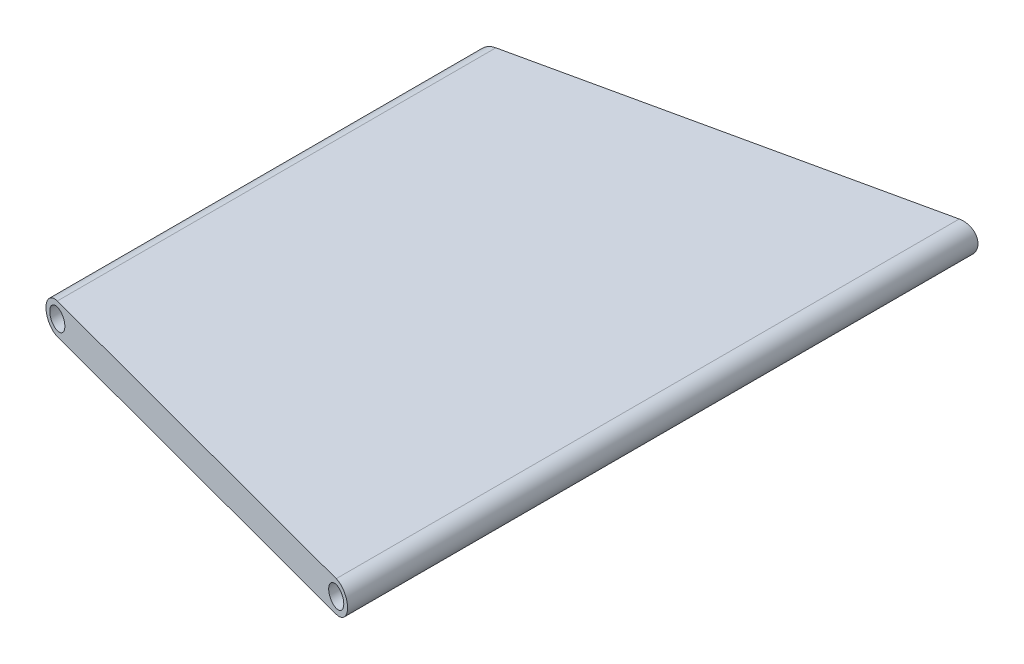
SolidWorks part; units mm, degrees
material "Balsa"
ref_plane "Front Plane" through (0, 0, 0) normal (0, 0, 1) x (1, 0, 0)
ref_plane "Top Plane" through (0, 0, 0) normal (0, 1, 0) x (1, 0, 0)
ref_plane "Right Plane" through (0, 0, 0) normal (1, 0, 0) x (0, 0, -1)
sketch "Sketch1" plane through (0, 0, 0) normal (0, 1, 0) x (1, 0, 0)
  line L0 (-43.5749, 0) -> (30.4251, 0)
  line L1 (30.4251, 0) -> (30.4251, 60.6725)
  line L2 (30.4251, 60.6725) -> (30.4251, 0)
  line L3 (30.4251, 0) -> (30.4251, -60.6725)
  line L4 (30.4251, -60.6725) -> (30.4251, 0)
  line L5 (-43.5749, 0) -> (-43.5749, 44.4209)
  line L6 (-43.5749, 44.4209) -> (30.4251, 60.6725)
  line L7 (-43.5749, -41) -> (-43.5749, 0)
  line L8 (-43.5749, -41) -> (30.4251, -60.6725)
  dimension "D1" = 41
  dimension "D2" = 74
extrude "Boss-Extrude1" add sketch "Sketch1" along normal mid plane 6 contours L7 L8 L3 L0 | L6 L5 L0 L1 region at (-4.6677, 0, -26.4828) region at (-4.1885, 0, 25.7353)
sketch "Sketch2" plane through (0, 0, 0) normal (0, 0, 1) x (1, 0, 0)
  line L0 (30.4251, 3) -> (30.4251, -3) construction
  line L1 (-43.5749, 3) -> (-43.5749, -3) construction
  circle A0 centre (30.4251, 0) radius 2
  circle A1 centre (30.4251, 0) radius 3
  circle A2 centre (-43.5749, 0) radius 2
  circle A3 centre (-43.5749, 0) radius 3
extrude "Boss-Extrude2" add sketch "Sketch2" along normal up to surface (61.47 mm away) contours A1 | A3 up to face at (-6.5749, 0, 50.8362)
extrude "Boss-Extrude3" add sketch "Sketch2<3>" against normal up to surface (61.1117 mm away) up to face at (-6.5749, 0, -52.5467)
sketch "Sketch2<3>" plane through (0, 0, 0) normal (0, 0, 1) x (1, 0, 0) same geometry as "Sketch2"
extrude "Cut-Extrude1" cut sketch "Sketch2<4>" against normal mid plane 206 contours A0 | A2 region at (30.4251, 0, 0) region at (-43.5749, 0, 0)
sketch "Sketch2<4>" plane through (0, 0, 0) normal (0, 0, 1) x (1, 0, 0) same geometry as "Sketch2"
